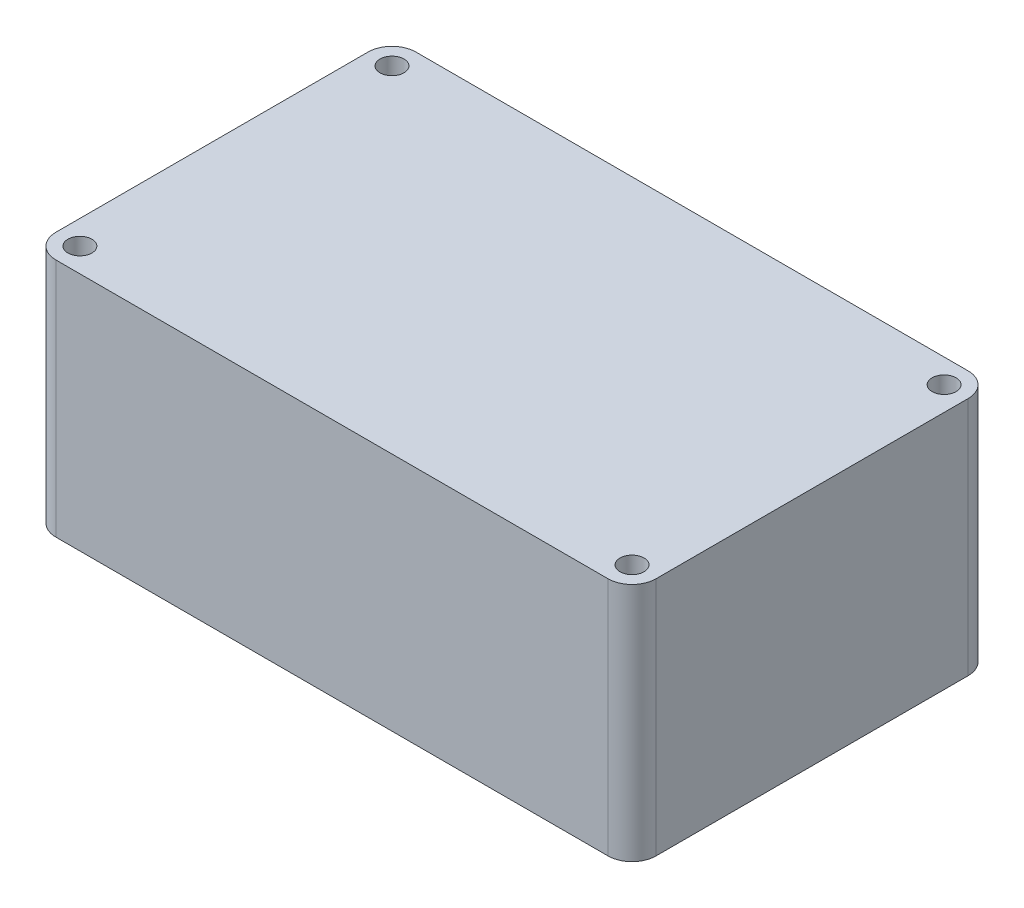
SolidWorks part; units mm, degrees
ref_plane "Alzado" through (0, 0, 0) normal (0, 0, 1) x (1, 0, 0)
ref_plane "Planta" through (0, 0, 0) normal (0, 1, 0) x (1, 0, 0)
ref_plane "Vista lateral" through (0, 0, 0) normal (1, 0, 0) x (0, 0, -1)
sketch "Croquis1" plane through (0, 0, 0) normal (0, 1, 0) x (1, 0, 0)
  line L0 (0, 75) -> (0, -75) construction
  line L1 (-125, 75) -> (125, 75)
  line L2 (-125, 75) -> (-125, -75)
  line L3 (-125, -75) -> (125, -75)
  line L4 (125, 75) -> (125, -75)
  dimension "D1" = 250
  dimension "D2" = 150
extrude "Saliente-Extruir1" add sketch "Croquis1" along normal blind 100
fillet "Redondeo1" radius 10 4 edges at (-125, 50, -75) (125, 50, -75) (125, 50, 75) (-125, 50, 75)
sketch "Croquis2" plane through (0, 100, 0) normal (0, 1, 0) x (1, 0, 0)
  circle A0 centre (-115, 65) radius 5
  dimension "D1" = 10
extrude "Cortar-Extruir1" cut sketch "Croquis2" against normal through all
mirror "Simetría1" about plane through (0, 0, 0) normal (0, 0, 1) of "Cortar-Extruir1" second plane through (0, 0, 0) second plane normal (1, 0, 0)
equation "\"Width\" = 250.0"
equation "\"Depth\" = 150.0"
equation "\"Height\" = 100.0"
equation "\"D1@Croquis1\"=\"Width\""
equation "\"D2@Croquis1\"=\"Depth\""
equation "\"D1@Saliente-Extruir1\"=\"Height\""
